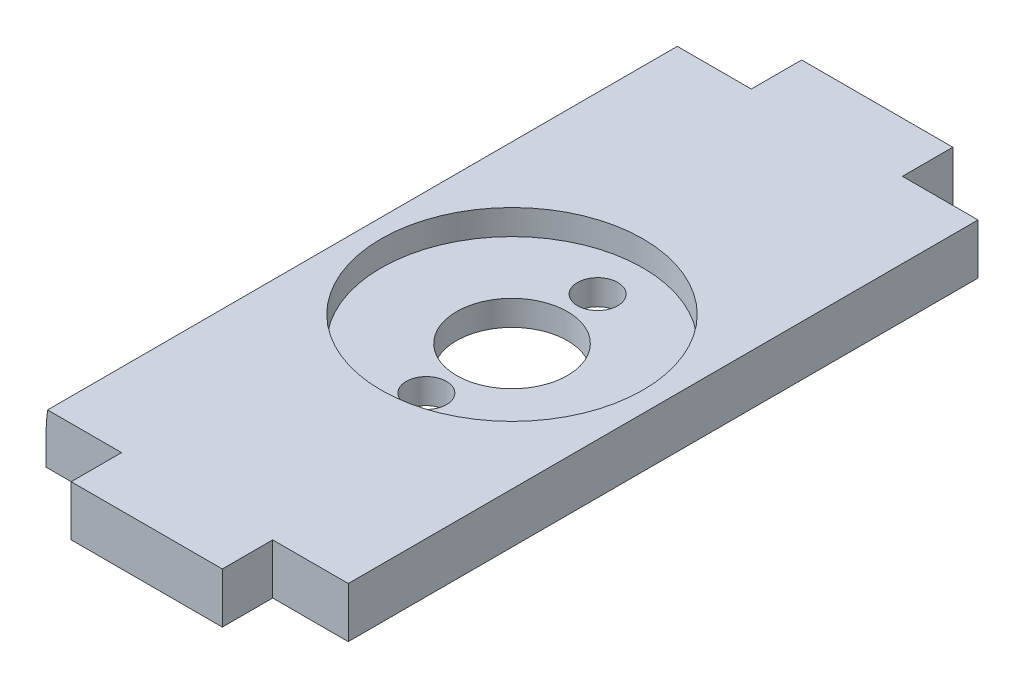
SolidWorks part; units mm, degrees
ref_plane "Front Plane" through (0, 0, 0) normal (0, 0, 1) x (1, 0, 0)
ref_plane "Top Plane" through (0, 0, 0) normal (0, 1, 0) x (1, 0, 0)
ref_plane "Right Plane" through (0, 0, 0) normal (1, 0, 0) x (0, 0, -1)
sketch "Sketch1" plane through (0, 0, 0) normal (0, 1, 0) x (1, 0, 0)
  line L0 (7.5, -31.25) -> (15, -31.25)
  line L1 (-15, -31.25) -> (-7.5, -31.25)
  line L2 (-15, -31.25) -> (-15, 31.25)
  line L3 (-15, 31.25) -> (-7.5, 31.25)
  line L4 (15, -31.25) -> (15, 31.25)
  line L5 (-15, -31.25) -> (15, 31.25) construction
  line L6 (-15, 31.25) -> (15, -31.25) construction
  line L8 (-7.5, -31.25) -> (-7.5, -36.25)
  line L9 (-7.5, -36.25) -> (7.5, -36.25)
  line L10 (7.5, -31.25) -> (7.5, -36.25)
  line L12 (-7.5, 31.25) -> (-7.5, 36.25)
  line L13 (-7.5, 36.25) -> (7.5, 36.25)
  line L14 (7.5, 31.25) -> (7.5, 36.25)
  line L15 (7.5, 31.25) -> (15, 31.25)
  circle A0 centre (0, 0) radius 5.5
  circle A1 centre (0, 8.5) radius 2
  circle A2 centre (0, -8.5) radius 2
  point P0 (0, 0)
  dimension "D4" = 5
  dimension "D1" = 30
  dimension "D2" = 8.5
  dimension "D3" = 8.5
  dimension "D5" = 15
  dimension "D6" = 7.5
  dimension "D7" = 5
  dimension "D8" = 62.5
extrude "Boss-Extrude1" add sketch "Sketch1" along normal blind 5
sketch "Sketch2" plane through (0, 5, 0) normal (0, 1, 0) x (1, 0, 0)
  circle A0 centre (0, 0) radius 13
extrude "Cut-Extrude1" cut sketch "Sketch2" against normal blind 2.5
sketch "Sketch3" plane through (0, 0, 31.25) normal (0, 0, 1) x (1, 0, 0)
  line L0 (-15, 5) -> (-7.5, 5) construction
  line L1 (-15, 5) -> (-15, 0) construction
  line L2 (-15, 5) -> (-15, 2.5)
  line L3 (-15, 5) -> (-14.8431, 5)
  arc A0 (-14.8431, 5) -> (-15, 2.5) centre (5, 2.5) ccw
  dimension "D1" = 2.5
  dimension "D2" = 20
extrude "Cut-Extrude2" cut sketch "Sketch3" against normal up to surface (62.5 mm away) up to face at (-11.25, 2.5, -31.25)
